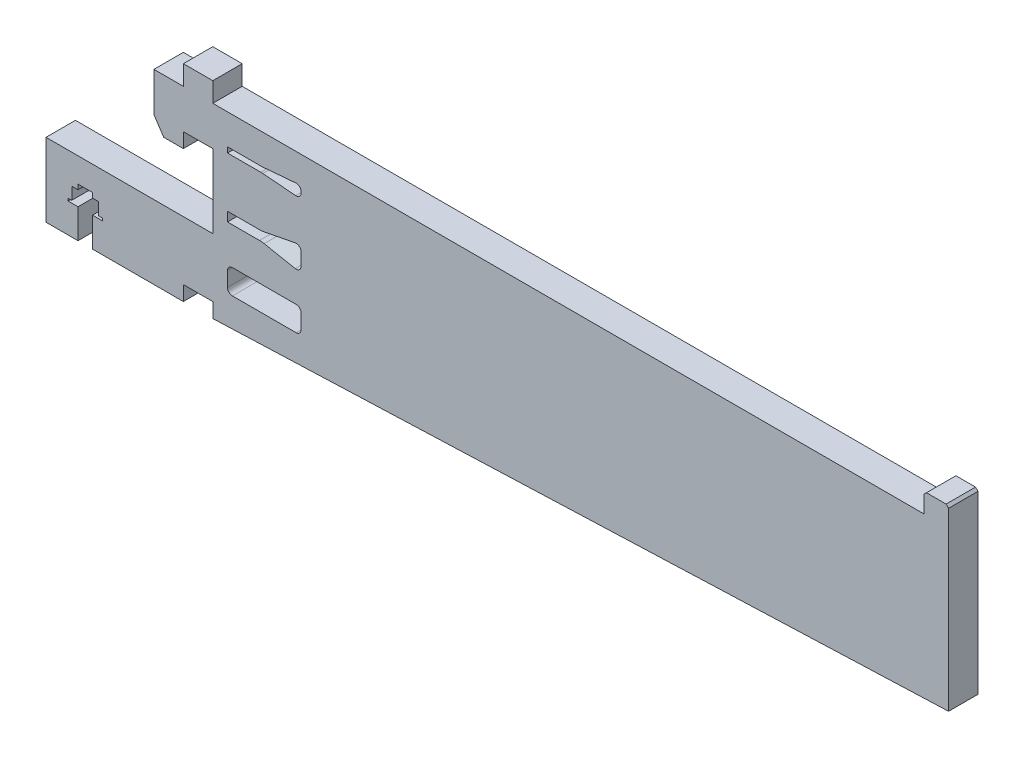
SolidWorks part; units mm, degrees
ref_plane "Front Plane" through (0, 0, 0) normal (0, 0, 1) x (1, 0, 0)
ref_plane "Top Plane" through (0, 0, 0) normal (0, 1, 0) x (1, 0, 0)
ref_plane "Right Plane" through (0, 0, 0) normal (1, 0, 0) x (0, 0, -1)
sketch "Sketch1" plane through (0, 0, 0) normal (0, 0, 1) x (1, 0, 0)
  line L0 (-17.5, -7) -> (16.5, -7)
  line L1 (16.5, -7) -> (16.5, 8)
  line L2 (16.5, 8) -> (10.5, 8)
  line L3 (10.5, 8) -> (10.5, 5)
  line L4 (10.5, 5) -> (4.5, 5)
  line L5 (4.5, 5) -> (4.5, 16)
  line L6 (4.5, 16) -> (10.5, 16)
  line L7 (166.5, 20) -> (166.5, -16.3429)
  line L8 (166.5, -16.3429) -> (16.5, -22)
  line L9 (10.5, -22) -> (-8.02, -22)
  line L10 (-18, 24.3801) -> (-18, -27.6715) construction
  line L11 (10.5, 16) -> (10.5, 20)
  line L12 (10.5, 20) -> (16.5, 20)
  line L13 (19.5, -2.5) -> (34.5, -2.5) construction
  line L14 (19.5, -3.45) -> (19.5, -1.55)
  line L15 (19.5, -1.55) -> (26.5, -1.55)
  line L16 (26.5, -1.55) -> (34.5, 0)
  line L17 (34.5, 0) -> (34.5, -5)
  line L18 (26.5, -3.45) -> (34.5, -5)
  line L19 (19.5, -3.45) -> (26.5, -3.45)
  line L20 (19.5, -13.5) -> (34.5, -13.5) construction
  line L21 (19.5, -16) -> (19.5, -11)
  line L22 (19.5, -11) -> (34.5, -11)
  line L23 (16.5, -22) -> (16.5, -19)
  line L24 (34.5, -11) -> (34.5, -16)
  line L25 (16.5, -19) -> (10.5, -19)
  line L26 (19.5, -16) -> (34.5, -16)
  line L27 (-9.5, -22) -> (-9.5, -12) construction
  line L28 (-10.98, -22) -> (-10.98, -16)
  line L29 (-10.98, -16) -> (-13, -16)
  line L30 (-13, -16) -> (-13, -15.5)
  line L31 (-13, -15.5) -> (-12.25, -15.5)
  line L32 (-12.25, -15.5) -> (-12.25, -13)
  line L33 (-12.25, -13) -> (-10.98, -13)
  line L34 (-10.98, -13) -> (-10.98, -12)
  line L35 (-10.98, -12) -> (-8.02, -12)
  line L36 (-8.02, -13) -> (-8.02, -12)
  line L37 (-6.75, -13) -> (-8.02, -13)
  line L38 (-6.75, -15.5) -> (-6.75, -13)
  line L39 (-6, -15.5) -> (-6.75, -15.5)
  line L40 (-6, -16) -> (-6, -15.5)
  line L41 (-8.02, -16) -> (-6, -16)
  line L42 (-8.02, -22) -> (-8.02, -16)
  line L43 (-10.98, -22) -> (-17.5, -22)
  line L44 (13.5, 8) -> (13.5, -7) construction
  line L45 (16.5, 20) -> (16.5, 16)
  line L46 (16.5, 16) -> (161.5, 16)
  line L56 (-17.5, -22) -> (-17.5, -7)
  line L57 (161.5, 16) -> (161.5, 20)
  line L58 (161.5, 20) -> (166.5, 20)
  line L59 (19.5, 9.2767) -> (34.5, 9.2767) construction
  line L60 (19.5, 8.7267) -> (19.5, 9.8267)
  line L61 (19.5, 9.8267) -> (26.5, 9.8267)
  line L62 (26.5, 9.8267) -> (34.5, 10.4876)
  line L63 (34.5, 10.4876) -> (34.5, 8.0658)
  line L64 (26.5, 8.7267) -> (34.5, 8.0658)
  line L65 (19.5, 8.7267) -> (26.5, 8.7267)
  line L66 (10.5, -19) -> (10.5, -22)
  line L67 (27, -2.5) -> (27, -13.5) construction
  circle A0 centre (0, 0) radius 6 construction
  point P76 (27, -8)
  dimension "D1" = 12
  dimension "D3" = 6
  dimension "D4" = 16.5
  dimension "D5" = 17.5
  dimension "D6" = 16
  dimension "D7" = 6
  dimension "D8" = 6
  dimension "D9" = 15
  dimension "D10" = 8
  dimension "D11" = 3
  dimension "D12" = 15
  dimension "D13" = 1.9
  dimension "D14" = 3
  dimension "D15" = 7
  dimension "D16" = 15
  dimension "D17" = 5
  dimension "D18" = 8
  dimension "D19" = 1.1
  dimension "D20" = 5
  dimension "D21" = 11
  dimension "D22" = 28.5
  dimension "D23" = 2.96
  dimension "D24" = 7
  dimension "D25" = 5.5
  dimension "D26" = 0.5
  dimension "D27" = 2.5
  dimension "D28" = 1
  dimension "D29" = 150
  dimension "D30" = 10
  dimension "D31" = 23
  dimension "D36" = 5
  dimension "D37" = 4
extrude "Boss-Extrude1" add sketch "Sketch1" along normal blind 6
chamfer "Chamfer1" distance 3 distance2 2 1 edges at (4.5, 5, 3) first distance on face at (4.5, 10.5, 3)
fillet "Fillet1" radius 1 8 edges at (34.5, -5, 3) (34.5, 0, 3) (34.5, 8.0658, 3) (34.5, 10.4876, 3) (34.5, -16, 3) (19.5, -16, 3) (19.5, -11, 3) (34.5, -11, 3)
fillet "Fillet2" radius 5 4 edges at (26.5, -1.55, 3) (26.5, -3.45, 3) (26.5, 8.7267, 3) (26.5, 9.8267, 3)
chamfer "Chamfer2" distance 0.5 angle 45 2 edges at (166.5, 20, 3) (161.5, 20, 3)
